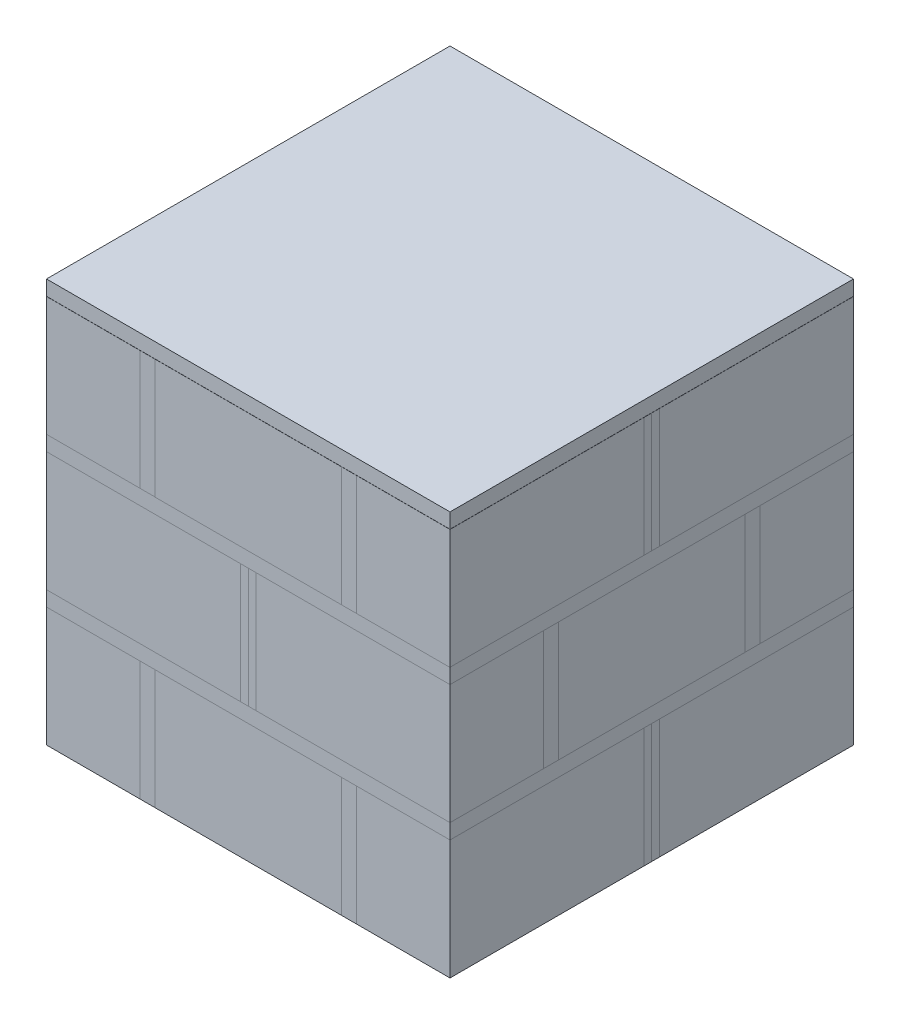
SolidWorks part; units mm, degrees
other "Камера1"
ref_plane "Спереди" through (0, 0, 0) normal (0, 0, 1) x (1, 0, 0)
ref_plane "Сверху" through (0, 0, 0) normal (0, 1, 0) x (1, 0, 0)
ref_plane "Справа" through (0, 0, 0) normal (1, 0, 0) x (0, 0, -1)
sketch "Эскиз2" plane through (0, 0, 0) normal (0, 1, 0) x (1, 0, 0)
  line L1 (13.435, -13.435) -> (-13.435, -13.435)
  line L2 (13.435, -13.435) -> (13.435, 13.435)
  line L3 (13.435, 13.435) -> (-13.435, 13.435)
  line L4 (-13.435, -13.435) -> (-13.435, 13.435)
  line L5 (13.435, -13.435) -> (-13.435, 13.435) construction
  line L6 (13.435, 13.435) -> (-13.435, -13.435) construction
  point P0 (0, 0)
  dimension "D1" = 38
  dimension "D2" = 26.8701
ref_plane "Плоскость1" through (0, 26.8701, 0) normal (0, 1, 0) x (1, 0, 0)
ref_plane "Плоскость2" through (0, 0, -13.435) normal (0, 0, 1) x (1, 0, 0)
ref_plane "Плоскость3" through (-13.435, 0, 0) normal (1, 0, 0) x (0, 0, -1)
extrude "Бобышка-Вытянуть1" [suppressed] add sketch "Эскиз2" along normal blind 26.87
pattern_linear "Линейный массив1" [suppressed] count 2 spacing 26.87 count 2 spacing 26.87 of bodies 108
sketch "Эскиз3" plane through (0, 0, 0) normal (0, 1, 0) x (1, 0, 0)
  line L0 (6.22, -0.5) -> (6.22, -13.435)
  line L5 (13.435, 13.435) -> (-13.435, 13.435)
  line L6 (13.435, 13.435) -> (13.435, -13.435)
  line L11 (13.435, -13.435) -> (-13.435, -13.435)
  line L12 (-13.435, 13.435) -> (-13.435, -13.435)
  line L21 (13.435, 13.435) -> (-13.435, -13.435) construction
  line L22 (13.435, -13.435) -> (-13.435, 13.435) construction
  line L23 (-13.435, 0) -> (13.435, 0)
  line L24 (-6.72, 0) -> (-6.72, -13.435)
  line L25 (-6.72, -13.435) -> (6.72, -13.435)
  line L26 (6.72, 0) -> (6.72, -13.435)
  line L27 (-6.22, -0.5) -> (6.22, -0.5)
  line L28 (-6.22, -0.5) -> (-6.22, -13.435)
  line L29 (-6.72, 0) -> (6.72, 0) construction
  line L30 (0, -13.435) -> (0, 0) construction
  line L31 (13.435, -0.5) -> (7.22, -0.5)
  line L32 (-13.435, -13.435) -> (-7.22, -13.435)
  line L33 (-13.435, -13.435) -> (-13.435, -0.5)
  line L34 (-13.435, -0.5) -> (-7.22, -0.5)
  line L35 (-7.22, -13.435) -> (-7.22, -0.5)
  line L36 (7.22, -13.435) -> (7.22, -0.5)
  point P0 (0, 0)
  dimension "D1" = 26.87
  dimension "D2" = 13.44
  dimension "D3" = 0.5
  dimension "D4" = 0.5
extrude "Бобышка-Вытянуть2" add sketch "Эскиз3" along normal blind 7.96 contours L11 L35 L34 L12 | L27 L28 L11 L0 | L36 L11 L6 L31 region at (0, 0, 6.9675) region at (10.3275, 0, 6.9675) region at (-10.3275, 0, 6.9675)
extrude "Бобышка-Вытянуть3" add sketch "Эскиз3<4>" along normal up to surface (7.96 mm away) separate body contours L28 L27 L0 L11 L26 L23 L24 L25 | L11 L36 L31 L6 L23 L26 | L35 L11 L24 L23 L12 L34 region at (0, 0, 0.31) region at (6.8702, 0, 6.7175) region at (-6.97, 0, 13.2848) up to face at (0, 7.96, 6.9675)
sketch "Эскиз3<4>" plane through (0, 0, 0) normal (0, 1, 0) x (1, 0, 0) same geometry as "Эскиз3"
mirror "Зеркальное отражение1" about plane through (0, 0, 0) normal (0, 0, 1) of bodies 211 136 209 210
sketch "Эскиз4" plane through (0, 7.96, 0) normal (0, 1, 0) x (1, 0, 0)
  line L1 (13.435, -13.435) -> (-13.435, -13.435)
  line L2 (13.435, -13.435) -> (13.435, 13.435)
  line L3 (13.435, 13.435) -> (-13.435, 13.435)
  line L4 (-13.435, -13.435) -> (-13.435, 13.435)
extrude "Бобышка-Вытянуть4" add sketch "Эскиз4" along normal blind 1 separate body
sketch "Эскиз6" plane through (0, 8.96, 0) normal (0, 1, 0) x (1, 0, 0)
  line L0 (0.5, 6.22) -> (13.435, 6.22)
  line L5 (-13.435, 13.435) -> (-13.435, -13.435)
  line L6 (-13.435, 13.435) -> (13.435, 13.435)
  line L11 (13.435, 13.435) -> (13.435, -13.435)
  line L12 (-13.435, -13.435) -> (13.435, -13.435)
  line L21 (-13.435, 13.435) -> (13.435, -13.435) construction
  line L22 (13.435, 13.435) -> (-13.435, -13.435) construction
  line L23 (0, -13.435) -> (0, 13.435)
  line L24 (0, -6.72) -> (13.435, -6.72)
  line L25 (13.435, -6.72) -> (13.435, 6.72)
  line L26 (0, 6.72) -> (13.435, 6.72)
  line L27 (0.5, -6.22) -> (0.5, 6.22)
  line L28 (0.5, -6.22) -> (13.435, -6.22)
  line L30 (13.435, 0) -> (0, 0) construction
  line L31 (0.5, 13.435) -> (0.5, 7.22)
  line L32 (13.435, -13.435) -> (13.435, -7.22)
  line L33 (13.435, -13.435) -> (0.5, -13.435)
  line L34 (0.5, -13.435) -> (0.5, -7.22)
  line L35 (13.435, -7.22) -> (0.5, -7.22)
  line L36 (13.435, 7.22) -> (0.5, 7.22)
  point P0 (0, 0)
  point P6 (0, 0)
  point P7 (0, 0)
  point P8 (0, 0)
  point P9 (0, 0)
  point P10 (0, 0)
  point P11 (0, 0)
  point P12 (0, 0)
  point P13 (0, 0)
  point P19 (0, 0)
  point P25 (0, 0)
  point P34 (12.2449, -4.899)
  point P35 (11.1424, 4.9074)
  point P36 (0, 0)
  line M43 (13.435, -13.435) -> (13.435, 13.435)
  line M44 (13.435, 13.435) -> (-13.435, 13.435)
  dimension "D1" = 26.87
  dimension "D2" = 13.44
  dimension "D3" = 0.5
  dimension "D4" = 0.5
  dimension "D5" = 0.5
extrude "Бобышка-Вытянуть5" add sketch "Эскиз6" along normal blind 7.96 separate body contours L35 L34 L12 M43 | L27 L28 L0 M43 | L36 L31 M43 M44 region at (6.9675, 8.96, 0) region at (6.9675, 8.96, -10.3275) region at (6.9675, 8.96, 10.3275)
extrude "Бобышка-Вытянуть6" add sketch "Эскиз6<6>" along normal up to surface (7.96 mm away) separate body contours L35 L11 L24 L23 L12 L34 | L28 L27 L0 L26 L23 L24 L11 M43 | L11 L36 L31 L6 L23 L26 region at (0.31, 8.96, 0) region at (6.7175, 8.96, -6.8702) region at (13.2848, 8.96, 6.97) up to face at (6.9675, 16.92, 0)
sketch "Эскиз6<6>" plane through (0, 8.96, 0) normal (0, 1, 0) x (1, 0, 0) same geometry as "Эскиз6"
mirror "Зеркальное отражение2" about plane through (0, 0, 0) normal (1, 0, 0) of bodies 218 219 217 220
pattern_linear "Линейный массив2" count 3 spacing 8.96 along (0, 1, 0) of "Бобышка-Вытянуть4"
pattern_linear "Линейный массив3" count 2 spacing 17.91 along (0, 1, 0) of bodies 209 210 136 213 215 214 211 212
equation "\"x\"= \"D2@Эскиз2\""
equation "\"half\"= \"D2@Эскиз2\" / 2"
